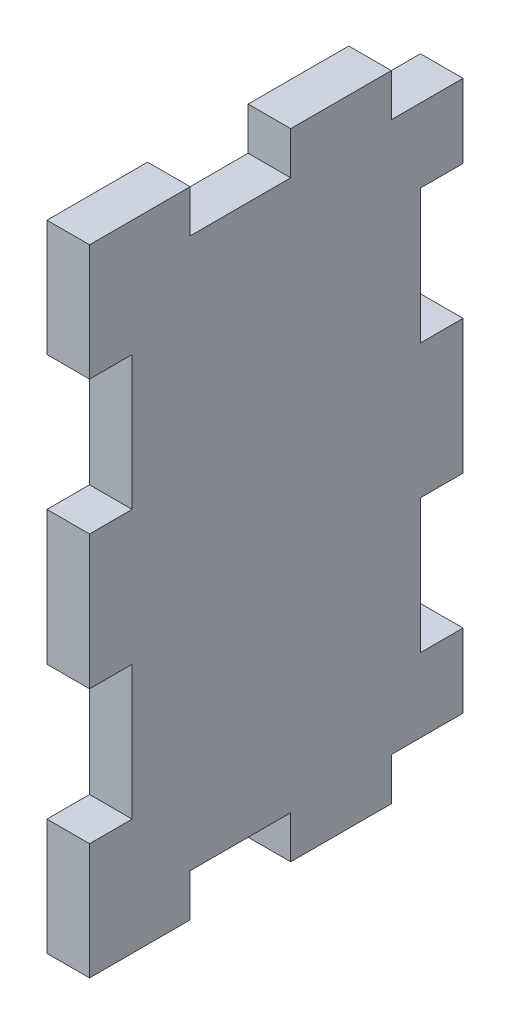
SolidWorks part; units mm, degrees
ref_plane "Front Plane" through (0, 0, 0) normal (0, 0, 1) x (1, 0, 0)
ref_plane "Top Plane" through (0, 0, 0) normal (0, 1, 0) x (1, 0, 0)
ref_plane "Right Plane" through (0, 0, 0) normal (1, 0, 0) x (0, 0, -1)
sketch "Sketch1" plane through (0, 0, 0) normal (1, 0, 0) x (0, 0, -1)
  line L1 (0, 0) -> (35.35, 0)
  line L2 (0, 0) -> (0, 47.35)
  line L3 (0, 47.35) -> (35.35, 47.35)
  line L4 (35.35, 0) -> (35.35, 47.35)
  dimension "D1" = 35.35
  dimension "D2" = 47.35
extrude "Boss-Extrude1" add sketch "Sketch1" along normal blind 3.175
sketch "Sketch2" plane through (0, 0, 0) normal (-1, 0, 0) x (0, 0, 1)
  line L0 (-35.35, 47.35) -> (0, 47.35) construction
  line L1 (-35.35, 47.35) -> (-27.85, 47.35)
  line L2 (-35.35, 47.35) -> (-35.35, 0)
  line L3 (-35.35, 0) -> (-27.85, 0)
  line L4 (-27.85, 47.35) -> (-27.85, 0)
  line L5 (-35.35, 0) -> (-35.35, 47.35) construction
  line L6 (0, 0) -> (-35.35, 0) construction
  dimension "D1" = 7.5
extrude "Cut-Extrude1" cut sketch "Sketch2" against normal through all
sketch "Sketch3" plane through (0, 0, 0) normal (-1, 0, 0) x (0, 0, 1)
  line L0 (0, 47.35) -> (0, 0) construction
  line L1 (-3.175, 8.675) -> (0, 8.675)
  line L2 (-3.175, 8.675) -> (-3.175, 18.675)
  line L3 (-3.175, 18.675) -> (0, 18.675)
  line L4 (0, 8.675) -> (0, 18.675)
  line L5 (-27.85, 0) -> (-27.85, 47.35) construction
  line L6 (-3.175, 28.675) -> (0, 28.675)
  line L7 (-3.175, 28.675) -> (-3.175, 38.675)
  line L8 (-3.175, 38.675) -> (0, 38.675)
  line L9 (0, 28.675) -> (0, 38.675)
  line L10 (-24.675, 8.675) -> (-27.85, 8.675)
  line L11 (-24.675, 8.675) -> (-24.675, 18.675)
  line L12 (-24.675, 18.675) -> (-27.85, 18.675)
  line L13 (-27.85, 8.675) -> (-27.85, 18.675)
  line L14 (-27.85, 47.35) -> (0, 47.35) construction
  line L15 (-24.675, 28.675) -> (-27.85, 28.675)
  line L16 (-24.675, 28.675) -> (-24.675, 38.675)
  line L17 (-24.675, 38.675) -> (-27.85, 38.675)
  line L18 (-27.85, 28.675) -> (-27.85, 38.675)
  line L19 (-7.5, 44.175) -> (-15, 44.175)
  line L20 (-7.5, 44.175) -> (-7.5, 47.35)
  line L21 (-7.5, 47.35) -> (-15, 47.35)
  line L22 (-15, 44.175) -> (-15, 47.35)
  line L23 (0, 0) -> (-27.85, 0) construction
  line L24 (-7.5, 3.175) -> (-15, 3.175)
  line L25 (-7.5, 3.175) -> (-7.5, 0)
  line L26 (-7.5, 0) -> (-15, 0)
  line L27 (-15, 3.175) -> (-15, 0)
  line L28 (-27.85, 0) -> (-27.85, 47.35) construction
  line L29 (-22.5, 44.175) -> (-27.85, 44.175)
  line L30 (-22.5, 44.175) -> (-22.5, 47.35)
  line L31 (-22.5, 47.35) -> (-27.85, 47.35)
  line L32 (-27.85, 44.175) -> (-27.85, 47.35)
  line L34 (-22.5, 3.175) -> (-27.85, 3.175)
  line L35 (-22.5, 3.175) -> (-22.5, 0)
  line L36 (-22.5, 0) -> (-27.85, 0)
  line L37 (-27.85, 3.175) -> (-27.85, 0)
  point P42 (0, 0)
  dimension "D1" = 7.5
  dimension "D2" = 7.5
  dimension "D3" = 7.5
  dimension "D4" = 3.175
  dimension "D5" = 10
  dimension "D6" = 10
  dimension "D7" = 8.675
  dimension "D8" = 3.175
extrude "Cut-Extrude2" cut sketch "Sketch3" against normal through all
